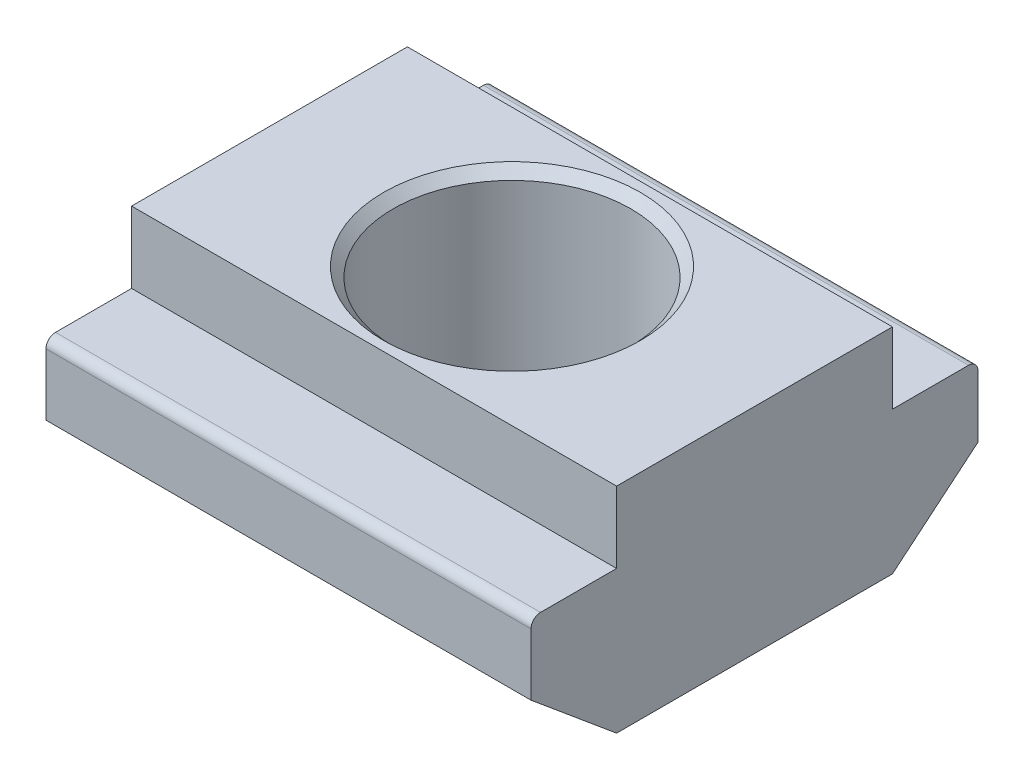
SolidWorks part; units mm, degrees
material "AISI 316 Stainless Steel Sheet (SS)"
ref_plane "Спереди" through (0, 0, 0) normal (0, 0, 1) x (1, 0, 0)
ref_plane "Сверху" through (0, 0, 0) normal (0, 1, 0) x (1, 0, 0)
ref_plane "Справа" through (0, 0, 0) normal (1, 0, 0) x (0, 0, -1)
sketch "Эскиз1" plane through (0, 0, 0) normal (1, 0, 0) x (0, 0, -1)
  line L0 (-2.9, 0) -> (2.9, 0)
  line L1 (-2.9, 0) -> (-4.7, 1.5)
  line L2 (-4.7, 1.5) -> (-4.7, 3)
  line L3 (-4.7, 3) -> (-2.9, 3)
  line L4 (-2.9, 3) -> (-2.9, 4.5)
  line L5 (-2.9, 4.5) -> (2.9, 4.5)
  line L6 (2.9, 4.5) -> (2.9, 3)
  line L7 (2.9, 3) -> (4.7, 3)
  line L8 (4.7, 3) -> (4.7, 1.5)
  line L9 (4.7, 1.5) -> (2.9, 0)
  line L10 (0, 0) -> (0, 3.8912) construction
  point P4 (0, 0)
  dimension "D1" = 5.8
  dimension "D2" = 4.5
  dimension "D3" = 1.5
  dimension "D4" = 1.5
  dimension "D5" = 1.5
  dimension "D6" = 1.5
  dimension "D7" = 5.8
  dimension "D8" = 9.4
extrude "Body" add sketch "Эскиз1" along normal blind 10.2
sketch "Эскиз2" plane through (0, 4.5, 0) normal (0, 1, 0) x (1, 0, 0)
  line L0 (0, 0) -> (10.8879, 0) construction
  line L1 (5.1, 4.7) -> (5.1, -4.7) construction
  line L2 (10.2, 4.7) -> (0, 4.7) construction
  line L3 (10.2, -4.7) -> (0, -4.7) construction
  circle A0 centre (5.1, 0) radius 2.5
  dimension "D1" = 5
extrude "Hole" cut sketch "Эскиз2" against normal blind 10.2
chamfer "Chamfer" distance 0.2 angle 45 1 edges at (5.1, 4.5, 2.5)
fillet "Fillet" radius 0.2 2 edges at (5.1, 3, 4.7) (5.1, 3, -4.7)
